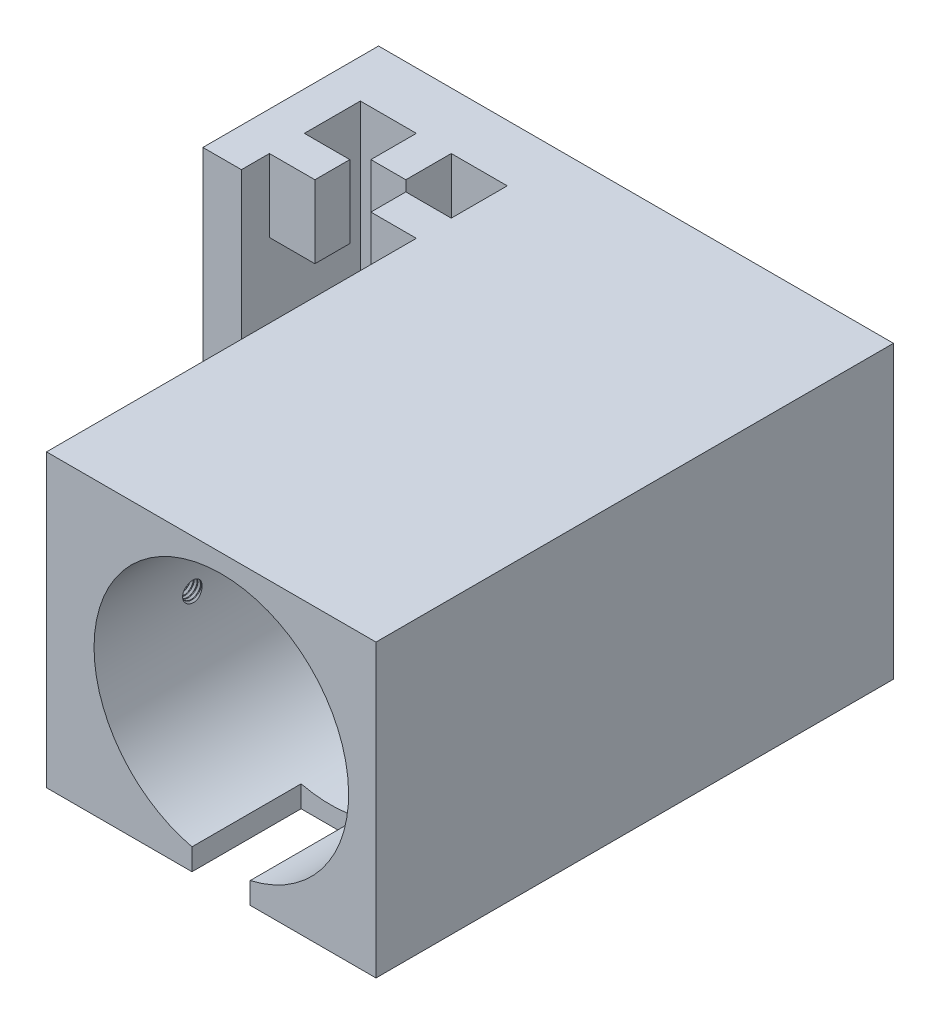
SolidWorks part; units mm, degrees
ref_plane "Plan de face" through (0, 0, 0) normal (0, 0, 1) x (1, 0, 0)
ref_plane "Plan de dessus" through (0, 0, 0) normal (0, 1, 0) x (1, 0, 0)
ref_plane "Plan de droite" through (0, 0, 0) normal (1, 0, 0) x (0, 0, -1)
sketch "Base" plane through (0, 0, 0) normal (0, 1, 0) x (1, 0, 0)
  line L0 (-3.85, -2.4) -> (-3.85, 2.4)
  line L1 (-3.85, 2.4) -> (-10.1, 2.4)
  line L2 (-10.1, 2.4) -> (-10.1, 10.1)
  line L3 (-10.1, 10.1) -> (-2.4, 10.1)
  line L4 (-2.4, 10.1) -> (-2.4, 3.85)
  line L5 (-2.4, 3.85) -> (2.4, 3.85)
  line L6 (0, -55) -> (0, 55) construction
  line L7 (2.4, 10.1) -> (2.4, 3.85)
  line L8 (10.1, 10.1) -> (2.4, 10.1)
  line L9 (10.1, 2.4) -> (10.1, 10.1)
  line L10 (3.85, 2.4) -> (10.1, 2.4)
  line L11 (3.85, -2.4) -> (3.85, 2.4)
  line L12 (-55, 0) -> (55, 0) construction
  line L13 (3.85, -2.4) -> (10.1, -2.4)
  line L14 (10.1, -2.4) -> (10.1, -6.25)
  line L20 (-10.1, -2.4) -> (-10.1, -6.25)
  line L21 (-3.85, -2.4) -> (-10.1, -2.4)
  line L23 (-15.4, 15.4) -> (15.4, 15.4)
  line L24 (-15.4, 15.4) -> (-15.4, -6.25)
  line L26 (15.4, 15.4) -> (15.4, -6.25)
  line L27 (-15.4, 15.4) -> (0, 0) construction
  line L28 (0, 0) -> (15.4, 15.4) construction
  line L29 (-10.1, -6.25) -> (-15.4, -6.25)
  line L30 (10.1, -6.25) -> (15.4, -6.25)
  line L31 (10.1, -10.1) -> (15.4, -15.4) construction
  point P2 (-3.85, 0)
  point P3 (0, 3.85)
  point P27 (0, 0)
  dimension "D1" = 4.8
  dimension "D2" = 4.8
  dimension "D3" = 6.25
  dimension "D4" = 7.7
  dimension "D5" = 30.8
extrude "Boss.-Extru.1" add sketch "Base" along normal mid plane 40
sketch "Esquisse6" plane through (0, 0, 0) normal (0, 0, 1) x (1, 0, 0)
  line L0 (10.1, 20) -> (10.1, -20) construction
  line L1 (-10.1, 10) -> (10.1, 10)
  line L2 (-10.1, 10) -> (-10.1, -10)
  line L3 (-10.1, -10) -> (10.1, -10)
  line L4 (10.1, 10) -> (10.1, -10)
  line L5 (-10.1, 10) -> (10.1, -10) construction
  line L6 (-10.1, -10) -> (10.1, 10) construction
  point P0 (0, 0)
  dimension "D1" = 20
extrude "Enlèv. mat.-Extru.1" cut sketch "Esquisse6" against normal mid plane 6
sketch "Esquisse14" plane through (0, -20, 0) normal (0, -1, 0) x (1, 0, 0)
  line L0 (15.4, 6.25) -> (15.4, -15.4) construction
  line L1 (-15.4, -15.4) -> (15.4, -15.4)
  line L2 (-15.4, -15.4) -> (-15.4, -17.9)
  line L3 (-15.4, -17.9) -> (15.4, -17.9)
  line L4 (15.4, -15.4) -> (15.4, -17.9)
  dimension "D1" = 2.5
extrude "Boss.-Extru.3" add sketch "Esquisse14" against normal up to vertex (40 mm away)
chamfer "Chanfrein1" distance 6.25 angle 45 2 edges at (3.85, -10, 0) (-3.85, -10, 0)
sketch "Esquisse16" plane through (15.4, 0, 0) normal (1, 0, 0) x (0, 0, -1)
  line L0 (-6.25, -20) -> (17.9, -20) construction
  line L1 (-6.25, 20) -> (17.9, 20)
  line L2 (-6.25, 20) -> (-6.25, -20)
  line L3 (-6.25, -20) -> (17.9, -20)
  line L4 (17.9, 20) -> (17.9, -20)
  line L5 (17.9, 20) -> (17.9, -20) construction
  line L6 (-6.25, 20) -> (-6.25, -20) construction
  dimension "D1" = 0
  dimension "D2" = 0
  dimension "D3" = 0
  dimension "D4" = 0
extrude "Boss.-Extru.4" add sketch "Esquisse16" along normal blind 40
sketch "Esquisse17" plane through (0, 0, -17.9) normal (0, 0, -1) x (-1, 0, 0)
  line L0 (15.4, 20) -> (-55.4, 20) construction
  circle A0 centre (-34.1338, 0) radius 17.5
  dimension "D1" = 20
sketch "Esquisse18" plane through (0, 0, 6.25) normal (0, 0, 1) x (1, 0, 0)
  line L0 (10.1, 20) -> (55.4, 20) construction
  line L1 (10.1, 20) -> (55.4, 20)
  line L2 (10.1, 20) -> (10.1, -20)
  line L3 (10.1, -20) -> (55.4, -20)
  line L4 (55.4, 20) -> (55.4, -20)
  line L5 (55.4, 20) -> (55.4, -20) construction
  line L6 (10.1, -20) -> (55.4, -20) construction
  line L7 (10.1, 20) -> (10.1, -20) construction
  dimension "D1" = 0
  dimension "D2" = 0
  dimension "D3" = 0
  dimension "D4" = 0
extrude "Boss.-Extru.5" add sketch "Esquisse18" along normal blind 47
extrude "Enlèv. mat.-Extru.4" cut sketch "Esquisse17" against normal blind 73
sketch "Esquisse19" plane through (0, -20, 0) normal (0, -1, 0) x (-1, 0, 0)
  line L0 (-10.1, -2.4) -> (-10.1, -53.25) construction
  line L1 (-30.1, -53.25) -> (-38.1, -53.25)
  line L2 (-30.1, -53.25) -> (-30.1, -38.25)
  line L3 (-30.1, -38.25) -> (-38.1, -38.25)
  line L4 (-38.1, -53.25) -> (-38.1, -38.25)
  line L5 (-10.1, -53.25) -> (-55.4, -53.25) construction
  dimension "D1" = 15
  dimension "D2" = 8
  dimension "D3" = 20
  dimension "D4" = 0
extrude "Enlèv. mat.-Extru.5" cut sketch "Esquisse19" against normal blind 6
sketch "Esquisse22" plane through (10.1, 0, 0) normal (-1, 0, 0) x (0, 0, 1)
  line L0 (2.4, 20) -> (53.25, 20) construction
  circle A0 centre (39.6977, 0) radius 4
  dimension "D1" = 20
extrude "Enlèv. mat.-Extru.6" cut sketch "Esquisse22" against normal blind 1 contours A0
sketch "Esquisse23" plane through (11.1, 0, 0) normal (-1, 0, 0) x (0, 0, 1)
  circle A0 centre (39.6977, 0) radius 1.25
  circle A2 centre (39.6977, 0) radius 4 construction
  dimension "D1" = 0
extrude "Enlèv. mat.-Extru.7" cut sketch "Esquisse23" against normal blind 7 contours A0
chamfer "Chanfrein4" distance 0.25 angle 45 1 edges at (11.1, 0, 40.9477)
sketch "Esquisse54" plane through (10.1, 0, 0) normal (-1, 0, 0) x (0, 0, 1)
  circle A0 centre (39.6977, 0) radius 1.6
curve "Hélice/Spirale1" pitch 0.5 height 10 turns 20
sketch "Esquisse55" plane through (0, 0, 0) normal (0, 1, 0) x (1, 0, 0)
  line L0 (14.9838, -38.4485) -> (14.5912, -38.4485)
  line L1 (14.5912, -38.4485) -> (14.7847, -38.1985)
  line L2 (14.7847, -38.1985) -> (14.9838, -38.4485)
  line L3 (14.7847, -38.1985) -> (14.7847, -38.4485)
  spline S0 degree 3 poles (10.1, -38.5663) (10.1104, -38.7135) (10.1313, -39.0699) (10.1625, -39.6976) (10.1938, -40.326) (10.225, -40.8585) (10.2563, -41.2144) (10.2875, -41.3393) (10.3188, -41.2144) (10.35, -40.8585) (10.3917, -40.1484) (10.4333, -39.247) (10.475, -38.5369) (10.5063, -38.181) (10.5375, -38.056) (10.5688, -38.181) (10.6, -38.5369) (10.6417, -39.247) (10.6833, -40.1484) (10.725, -40.8585) (10.7562, -41.2144) (10.7875, -41.3393) (10.8187, -41.2144) (10.85, -40.8585) (10.8917, -40.1484) (10.9333, -39.247) (10.975, -38.5369) (11.0063, -38.181) (11.0375, -38.056) (11.0687, -38.181) (11.1, -38.5369) (11.1417, -39.247) (11.1833, -40.1484) (11.225, -40.8585) (11.2563, -41.2144) (11.2875, -41.3393) (11.3188, -41.2144) (11.35, -40.8585) (11.3917, -40.1484) (11.4333, -39.247) (11.475, -38.5369) (11.5062, -38.181) (11.5375, -38.056) (11.5688, -38.181) (11.6, -38.5369) (11.6417, -39.247) (11.6833, -40.1484) (11.725, -40.8585) (11.7562, -41.2144) (11.7875, -41.3393) (11.8188, -41.2144) (11.85, -40.8585) (11.8917, -40.1484) (11.9333, -39.247) (11.975, -38.5369) (12.0063, -38.181) (12.0375, -38.056) (12.0688, -38.181) (12.1, -38.5369) (12.1417, -39.247) (12.1833, -40.1484) (12.225, -40.8585) (12.2563, -41.2144) (12.2875, -41.3393) (12.3187, -41.2144) (12.35, -40.8585) (12.3917, -40.1484) (12.4333, -39.247) (12.475, -38.5369) (12.5063, -38.181) (12.5375, -38.056) (12.5688, -38.181) (12.6, -38.5369) (12.6417, -39.247) (12.6833, -40.1484) (12.725, -40.8585) (12.7563, -41.2144) (12.7875, -41.3393) (12.8188, -41.2144) (12.85, -40.8585) (12.8917, -40.1484) (12.9333, -39.247) (12.975, -38.5369) (13.0063, -38.181) (13.0375, -38.056) (13.0688, -38.181) (13.1, -38.5369) (13.1417, -39.247) (13.1833, -40.1484) (13.225, -40.8585) (13.2563, -41.2144) (13.2875, -41.3393) (13.3188, -41.2144) (13.35, -40.8585) (13.3917, -40.1484) (13.4333, -39.247) (13.475, -38.5369) (13.5063, -38.181) (13.5375, -38.056) (13.5688, -38.181) (13.6, -38.5369) (13.6417, -39.247) (13.6833, -40.1484) (13.725, -40.8585) (13.7563, -41.2144) (13.7875, -41.3393) (13.8188, -41.2144) (13.85, -40.8585) (13.8917, -40.1484) (13.9333, -39.247) (13.975, -38.5369) (14.0063, -38.181) (14.0375, -38.056) (14.0688, -38.181) (14.1, -38.5369) (14.1417, -39.247) (14.1833, -40.1484) (14.225, -40.8585) (14.2563, -41.2144) (14.2875, -41.3393) (14.3187, -41.2144) (14.35, -40.8585) (14.3917, -40.1484) (14.4333, -39.247) (14.475, -38.5369) (14.5062, -38.181) (14.5375, -38.056) (14.5688, -38.181) (14.6, -38.5369) (14.6417, -39.247) (14.6833, -40.1484) (14.725, -40.8585) (14.7562, -41.2144) (14.7875, -41.3393) (14.8188, -41.2144) (14.85, -40.8585) (14.8917, -40.1484) (14.9333, -39.247) (14.975, -38.5369) (15.0063, -38.181) (15.0375, -38.056) (15.0688, -38.181) (15.1, -38.5369) (15.1417, -39.247) (15.1833, -40.1484) (15.225, -40.8585) (15.2563, -41.2144) (15.2875, -41.3393) (15.3187, -41.2144) (15.35, -40.8585) (15.3917, -40.1484) (15.4333, -39.247) (15.475, -38.5369) (15.5063, -38.181) (15.5375, -38.056) (15.5688, -38.181) (15.6, -38.5369) (15.6417, -39.247) (15.6833, -40.1484) (15.725, -40.8585) (15.7563, -41.2144) (15.7875, -41.3393) (15.8188, -41.2144) (15.85, -40.8585) (15.8917, -40.1484) (15.9333, -39.247) (15.975, -38.5369) (16.0063, -38.181) (16.0375, -38.056) (16.0688, -38.181) (16.1, -38.5369) (16.1417, -39.247) (16.1833, -40.1484) (16.225, -40.8585) (16.2563, -41.2144) (16.2875, -41.3393) (16.3188, -41.2144) (16.35, -40.8585) (16.3917, -40.1484) (16.4333, -39.247) (16.475, -38.5369) (16.5063, -38.181) (16.5375, -38.056) (16.5688, -38.181) (16.6, -38.5369) (16.6417, -39.247) (16.6833, -40.1484) (16.725, -40.8585) (16.7563, -41.2144) (16.7875, -41.3393) (16.8188, -41.2144) (16.85, -40.8585) (16.8917, -40.1484) (16.9333, -39.247) (16.975, -38.5369) (17.0063, -38.181) (17.0375, -38.056) (17.0688, -38.181) (17.1, -38.5369) (17.1417, -39.247) (17.1833, -40.1484) (17.225, -40.8585) (17.2563, -41.2144) (17.2875, -41.3393) (17.3188, -41.2144) (17.35, -40.8585) (17.3917, -40.1484) (17.4333, -39.247) (17.475, -38.5369) (17.5063, -38.181) (17.5375, -38.056) (17.5688, -38.181) (17.6, -38.5369) (17.6417, -39.247) (17.6833, -40.1484) (17.725, -40.8585) (17.7563, -41.2144) (17.7875, -41.3393) (17.8188, -41.2144) (17.85, -40.8585) (17.8917, -40.1484) (17.9333, -39.247) (17.975, -38.5369) (18.0063, -38.181) (18.0375, -38.056) (18.0688, -38.181) (18.1, -38.5369) (18.1417, -39.247) (18.1833, -40.1484) (18.225, -40.8585) (18.2563, -41.2144) (18.2875, -41.3393) (18.3188, -41.2144) (18.35, -40.8585) (18.3917, -40.1484) (18.4333, -39.247) (18.475, -38.5369) (18.5063, -38.181) (18.5375, -38.056) (18.5688, -38.181) (18.6, -38.5369) (18.6417, -39.247) (18.6833, -40.1484) (18.725, -40.8585) (18.7563, -41.2144) (18.7875, -41.3393) (18.8188, -41.2144) (18.85, -40.8585) (18.8917, -40.1484) (18.9333, -39.247) (18.975, -38.5369) (19.0063, -38.181) (19.0375, -38.056) (19.0688, -38.181) (19.1, -38.5369) (19.1417, -39.247) (19.1833, -40.1484) (19.225, -40.8585) (19.2563, -41.2144) (19.2875, -41.3393) (19.3188, -41.2144) (19.35, -40.8585) (19.3917, -40.1484) (19.4333, -39.247) (19.475, -38.5369) (19.5063, -38.181) (19.5375, -38.056) (19.5687, -38.181) (19.6, -38.5369) (19.6417, -39.247) (19.6833, -40.1484) (19.725, -40.8585) (19.7562, -41.2144) (19.7875, -41.3393) (19.8187, -41.2144) (19.85, -40.8585) (19.8917, -40.1484) (19.9333, -39.247) (19.975, -38.5369) (20.0062, -38.181) (20.0375, -38.0562) (20.0687, -38.1806) (20.0896, -38.4192) (20.1, -38.5663) knots 0 0 0 0 0.003125 0.00625 0.009375 0.0125 0.015625 0.01875 0.021875 0.025 0.028125 0.034375 0.0375 0.040625 0.04375 0.046875 0.05 0.053125 0.059375 0.0625 0.065625 0.06875 0.071875 0.075 0.078125 0.084375 0.0875 0.090625 0.09375 0.096875 0.1 0.103125 0.109375 0.1125 0.115625 0.11875 0.121875 0.125 0.128125 0.134375 0.1375 0.140625 0.14375 0.146875 0.15 0.153125 0.159375 0.1625 0.165625 0.16875 0.171875 0.175 0.178125 0.184375 0.1875 0.190625 0.19375 0.196875 0.2 0.203125 0.209375 0.2125 0.215625 0.21875 0.221875 0.225 0.228125 0.234375 0.2375 0.240625 0.24375 0.246875 0.25 0.253125 0.259375 0.2625 0.265625 0.26875 0.271875 0.275 0.278125 0.284375 0.2875 0.290625 0.29375 0.296875 0.3 0.303125 0.309375 0.3125 0.315625 0.31875 0.321875 0.325 0.328125 0.334375 0.3375 0.340625 0.34375 0.346875 0.35 0.353125 0.359375 0.3625 0.365625 0.36875 0.371875 0.375 0.378125 0.384375 0.3875 0.390625 0.39375 0.396875 0.4 0.403125 0.409375 0.4125 0.415625 0.41875 0.421875 0.425 0.428125 0.434375 0.4375 0.440625 0.44375 0.446875 0.45 0.453125 0.459375 0.4625 0.465625 0.46875 0.471875 0.475 0.478125 0.484375 0.4875 0.490625 0.49375 0.496875 0.5 0.503125 0.509375 0.5125 0.515625 0.51875 0.521875 0.525 0.528125 0.534375 0.5375 0.540625 0.54375 0.546875 0.55 0.553125 0.559375 0.5625 0.565625 0.56875 0.571875 0.575 0.578125 0.584375 0.5875 0.590625 0.59375 0.596875 0.6 0.603125 0.609375 0.6125 0.615625 0.61875 0.621875 0.625 0.628125 0.634375 0.6375 0.640625 0.64375 0.646875 0.65 0.653125 0.659375 0.6625 0.665625 0.66875 0.671875 0.675 0.678125 0.684375 0.6875 0.690625 0.69375 0.696875 0.7 0.703125 0.709375 0.7125 0.715625 0.71875 0.721875 0.725 0.728125 0.734375 0.7375 0.740625 0.74375 0.746875 0.75 0.753125 0.759375 0.7625 0.765625 0.76875 0.771875 0.775 0.778125 0.784375 0.7875 0.790625 0.79375 0.796875 0.8 0.803125 0.809375 0.8125 0.815625 0.81875 0.821875 0.825 0.828125 0.834375 0.8375 0.840625 0.84375 0.846875 0.85 0.853125 0.859375 0.8625 0.865625 0.86875 0.871875 0.875 0.878125 0.884375 0.8875 0.890625 0.89375 0.896875 0.9 0.903125 0.909375 0.9125 0.915625 0.91875 0.921875 0.925 0.928125 0.934375 0.9375 0.940625 0.94375 0.946875 0.95 0.953125 0.959375 0.9625 0.965625 0.96875 0.971875 0.975 0.978125 0.984375 0.9875 0.990625 0.99375 0.996875 1 1 1 1 construction
  point P4 (14.7885, -38.4568)
  point P7 (14.7851, -38.0705)
  dimension "D1" = 0.25
sweep "Enlèvement de matière-Balayage1" cut profiles "Esquisse55" path "Hélice/Spirale1"
